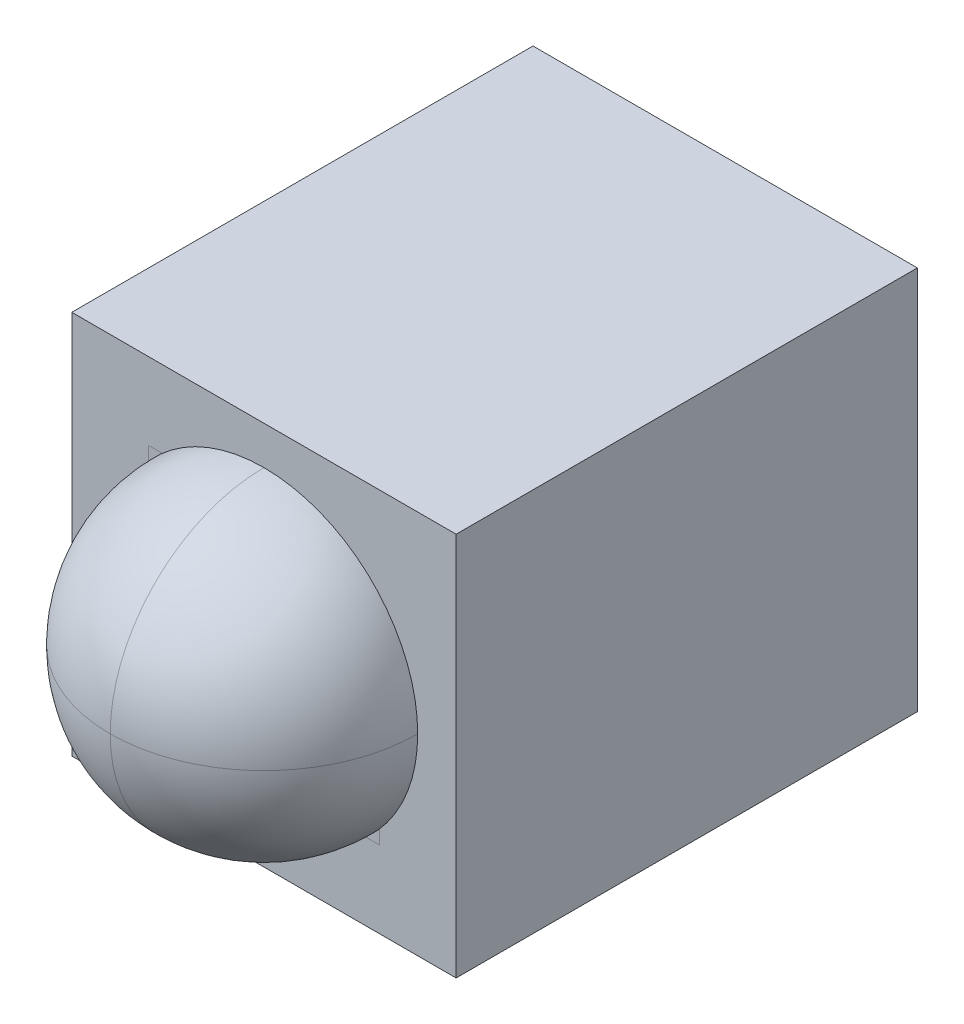
SolidWorks part; units mm, degrees
ref_plane "Front Plane" through (0, 0, 0) normal (0, 0, 1) x (1, 0, 0)
ref_plane "Top Plane" through (0, 0, 0) normal (0, 1, 0) x (1, 0, 0)
ref_plane "Right Plane" through (0, 0, 0) normal (1, 0, 0) x (0, 0, -1)
sketch "Sketch1" plane through (0, 0, 0) normal (0, 0, 1) x (1, 0, 0)
  line L1 (1.25, -1.25) -> (-1.25, -1.25)
  line L2 (1.25, -1.25) -> (1.25, 1.25)
  line L3 (1.25, 1.25) -> (-1.25, 1.25)
  line L4 (-1.25, -1.25) -> (-1.25, 1.25)
  line L5 (1.25, -1.25) -> (-1.25, 1.25) construction
  line L6 (1.25, 1.25) -> (-1.25, -1.25) construction
  line L7 (-0.75, -0.75) -> (0.75, -0.75)
  line L8 (-0.75, -0.75) -> (-0.75, 0.75)
  line L9 (-0.75, 0.75) -> (0.75, 0.75)
  line L10 (0.75, -0.75) -> (0.75, 0.75)
  line L11 (-0.75, -0.75) -> (0.75, 0.75) construction
  line L12 (-0.75, 0.75) -> (0.75, -0.75) construction
  point P0 (0, 0)
  point P6 (0, 0)
  dimension "D1" = 2.5
  dimension "D2" = 0.5
extrude "Boss-Extrude1" add sketch "Sketch1" along normal blind 3
sketch "Sketch2" plane through (0, 0, 3) normal (0, 0, 1) x (1, 0, 0)
  line L1 (1, -1) -> (-1, -1)
  line L2 (1, -1) -> (1, 1)
  line L3 (1, 1) -> (-1, 1)
  line L4 (-1, -1) -> (-1, 1)
  line L5 (1, -1) -> (-1, 1) construction
  line L6 (1, 1) -> (-1, -1) construction
  circle A0 centre (0, 0) radius 1 construction
  dimension "D1" = 2
extrude "Boss-Extrude3" add sketch "Sketch2" along normal blind 1 contours L3 L4 L1 L2
fillet "Fillet1" radius 1 4 edges at (0, -1, 4) (1, 0, 4) (0, 1, 4) (-1, 0, 4)
fillet "Fillet2" radius 1 4 edges at (0.7071, 0.7071, 3.7071) (0.7071, -0.7071, 3.7071) (-0.7071, -0.7071, 3.7071) (-0.7071, 0.7071, 3.7071)
